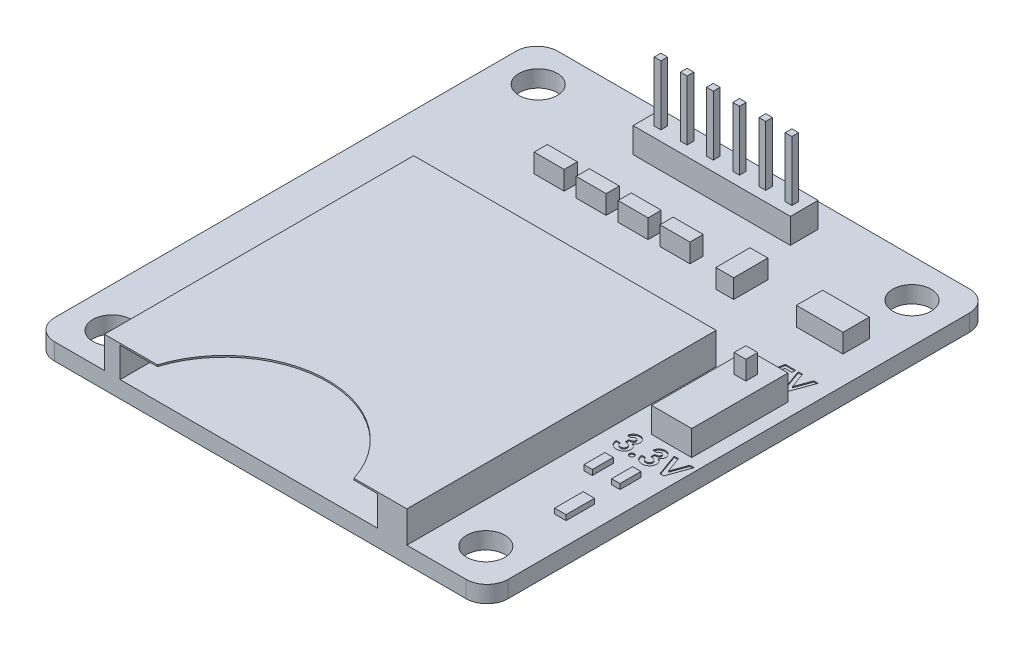
SolidWorks part; units mm, degrees
material "policarbonato"
ref_plane "Alzado" through (0, 0, 0) normal (0, 0, 1) x (1, 0, 0)
ref_plane "Planta" through (0, 0, 0) normal (0, 1, 0) x (1, 0, 0)
ref_plane "Vista lateral" through (0, 0, 0) normal (1, 0, 0) x (0, 0, -1)
sketch "Sketch1" plane through (0, 0, 0) normal (0, 1, 0) x (1, 0, 0)
  line L0 (3.8, 44.325) -> (39.45, 44.325) construction
  line L1 (0, 0) -> (43.25, 0)
  line L2 (0, 0) -> (0, 48)
  line L3 (0, 48) -> (43.25, 48)
  line L4 (43.25, 0) -> (43.25, 48)
  line L5 (39.45, 44.325) -> (39.45, 3.675) construction
  line L6 (39.45, 3.675) -> (3.8, 3.675) construction
  line L7 (3.8, 3.675) -> (3.8, 44.325) construction
  line L8 (21.625, 44.325) -> (21.625, 48) construction
  line L9 (39.45, 24) -> (43.25, 24) construction
  circle A0 centre (3.8, 44.325) radius 1.825
  circle A1 centre (3.8, 3.675) radius 1.825
  circle A2 centre (39.45, 44.325) radius 1.825
  circle A3 centre (39.45, 3.675) radius 1.825
  dimension "D3" = 3.65
  dimension "D4" = 32
  dimension "D5" = 37
  dimension "D6" = 40.65
  dimension "D7" = 35.65
  dimension "D1" = 43.25
  dimension "D2" = 48
extrude "Boss-Extrude1" add sketch "Sketch1" along normal blind 1.6
sketch "Sketch2" plane through (0, 1.6, 0) normal (0, 1, 0) x (1, 0, 0)
  line L0 (0, 0) -> (43.25, 0) construction
  line L1 (6.75, 0) -> (11.8, 0)
  line L2 (6.75, 0) -> (6.75, 29.5)
  line L3 (6.75, 29.5) -> (35.6, 29.5)
  line L4 (35.6, 0) -> (35.6, 29.5)
  line L6 (21.175, 29.5) -> (21.175, 0) construction
  line L7 (30.55, 0) -> (35.6, 0)
  line L9 (0, 48) -> (0, 0) construction
  arc A0 (11.8, 0) -> (30.55, 0) centre (21.175, -2.976) cw
  point P9 (21.175, 6.86)
  dimension "D1" = 6.75
  dimension "D2" = 29.5
  dimension "D3" = 6.86
  dimension "D4" = 18.75
  dimension "D5" = 28.85
extrude "Boss-Extrude2" add sketch "Sketch2" along normal offset from surface (3 mm away) 4.6 up to face at (39.45, 0, -42.5)
sketch "Sketch3" plane through (0, 0, 0) normal (0, 0, 1) x (1, 0, 0)
  line L0 (30.55, 1.6) -> (11.8, 1.6) construction
  line L1 (8.25, 1.6) -> (32.8, 1.6)
  line L2 (8.25, 1.6) -> (8.25, 4.45)
  line L3 (8.25, 4.45) -> (32.8, 4.45)
  line L4 (32.8, 1.6) -> (32.8, 4.45)
  line L5 (6.75, 4.6) -> (11.8, 4.6) construction
  line L6 (35.6, 4.6) -> (35.6, 1.6) construction
  line L7 (6.75, 4.6) -> (6.75, 1.6) construction
  point P8 (35.6, 3.1)
  dimension "D1" = 0.15
  dimension "D2" = 2.8
  dimension "D3" = 1.5
extrude "Cut-Extrude1" cut sketch "Sketch3" against normal blind 21.6
sketch "Sketch4" plane through (0, 1.6, 0) normal (0, 1, 0) x (1, 0, 0)
  line L0 (0, 38) -> (43.25, 38) construction
  line L1 (11, 38) -> (13.86, 38)
  line L2 (11, 38) -> (11, 36.74)
  line L3 (11, 36.74) -> (13.86, 36.74)
  line L4 (13.86, 38) -> (13.86, 36.74)
  line L5 (15, 38) -> (17.86, 38)
  line L6 (15, 38) -> (15, 36.74)
  line L7 (15, 36.74) -> (17.86, 36.74)
  line L8 (17.86, 38) -> (17.86, 36.74)
  line L9 (19, 38) -> (21.86, 38)
  line L10 (19, 38) -> (19, 36.74)
  line L11 (19, 36.74) -> (21.86, 36.74)
  line L12 (21.86, 38) -> (21.86, 36.74)
  line L13 (23, 38) -> (25.86, 38)
  line L14 (23, 38) -> (23, 36.74)
  line L15 (23, 36.74) -> (25.86, 36.74)
  line L16 (25.86, 38) -> (25.86, 36.74)
  line L17 (30.8926, 39.1335) -> (29.1926, 39.1335)
  line L18 (30.8926, 39.1335) -> (30.8926, 35.8735)
  line L19 (30.8926, 35.8735) -> (29.1926, 35.8735)
  line L20 (29.1926, 39.1335) -> (29.1926, 35.8735)
  line L21 (36.162, 39.0917) -> (40.612, 39.0917)
  line L22 (36.162, 39.0917) -> (36.162, 36.5917)
  line L23 (36.162, 36.5917) -> (40.612, 36.5917)
  line L24 (40.612, 39.0917) -> (40.612, 36.5917)
  line L25 (37.8886, 16.5953) -> (38.6886, 16.5953)
  line L26 (37.8886, 16.5953) -> (37.8886, 14.5953)
  line L27 (37.8886, 14.5953) -> (38.6886, 14.5953)
  line L28 (38.6886, 16.5953) -> (38.6886, 14.5953)
  line L29 (40.3717, 16.7505) -> (41.1717, 16.7505)
  line L30 (40.3717, 16.7505) -> (40.3717, 14.7505)
  line L31 (40.3717, 14.7505) -> (41.1717, 14.7505)
  line L32 (41.1717, 16.7505) -> (41.1717, 14.7505)
  line L33 (40.0854, 9.6117) -> (41.169, 9.6117)
  line L34 (40.0854, 9.6117) -> (40.0854, 12.3275)
  line L35 (40.0854, 12.3275) -> (41.169, 12.3275)
  line L36 (41.169, 9.6117) -> (41.169, 12.3275)
  line L37 (0, 48) -> (0, 0) construction
  line L38 (43.25, 0) -> (43.25, 48) construction
  line L39 (43.25, 48) -> (0, 48) construction
  dimension "D1" = 10
  dimension "D2" = 1.26
  dimension "D3" = 2.86
  dimension "D4" = 1.14
  dimension "D5" = 1.14
  dimension "D6" = 1.14
  dimension "D7" = 11
  dimension "D8" = 1.26
  dimension "D9" = 1.26
  dimension "D10" = 1.26
  dimension "D11" = 1.7
  dimension "D12" = 3.26
  dimension "D13" = 4.45
  dimension "D14" = 2.5
  dimension "D15" = 2
  dimension "D16" = 0.8
extrude "Boss-Extrude3" add sketch "Sketch4" along normal blind 1.8 contours L4 L1 L2 L3 | L8 L5 L6 L7 | L12 L9 L10 L11 | L16 L13 L14 L15 | L18 L19 L20 L17 | L24 L23 L22 L21 region at (12.43, 1.6, -37.37) region at (16.43, 1.6, -37.37) region at (20.43, 1.6, -37.37) region at (24.43, 1.6, -37.37)
extrude "Saliente-Extruir1" add sketch "Sketch4<3>" along normal blind 0.5 separate body contours L33 L36 L35 L34 | L32 L29 L30 L31 | L28 L25 L26 L27 region at (38.2886, 1.6, -15.5953) region at (40.7717, 1.6, -15.7505) region at (40.6272, 1.6, -10.9696)
sketch "Sketch4<3>" plane through (0, 1.6, 0) normal (0, 1, 0) x (1, 0, 0) same geometry as "Sketch4"
sketch "Sketch5" plane through (0, 1.6, 0) normal (0, 1, 0) x (1, 0, 0)
  line L0 (43.25, 0) -> (43.25, 48) construction
  line L1 (14.125, 45.7) -> (29.125, 45.7)
  line L2 (14.125, 45.7) -> (14.125, 43.05)
  line L3 (14.125, 43.05) -> (29.125, 43.05)
  line L4 (29.125, 45.7) -> (29.125, 43.05)
  line L5 (38.11, 30) -> (41.95, 30)
  line L6 (38.11, 30) -> (38.11, 20.82)
  line L7 (38.11, 20.82) -> (41.95, 20.82)
  line L8 (41.95, 30) -> (41.95, 20.82)
  line L9 (43.25, 48) -> (0, 48) construction
  line L10 (35.6, 29.5) -> (6.75, 29.5) construction
  line L12 (21.625, 45.7) -> (21.625, 48) construction
  dimension "D1" = 15
  dimension "D2" = 2.65
  dimension "D3" = 9.18
  dimension "D4" = 3.84
  dimension "D6" = 2.3
  dimension "D7" = 1.3
  dimension "D8" = 0.5
extrude "Boss-Extrude4" add sketch "Sketch5" along normal blind 2.4
sketch "Sketch6" plane through (0, 4, 0) normal (0, 1, 0) x (1, 0, 0)
  line L0 (14.125, 45.7) -> (14.125, 43.05) construction
  line L1 (15.165, 44.66) -> (15.805, 44.66)
  line L2 (15.165, 44.66) -> (15.165, 44.02)
  line L3 (15.165, 44.02) -> (15.805, 44.02)
  line L4 (15.805, 44.66) -> (15.805, 44.02)
  line L5 (29.125, 45.7) -> (14.125, 45.7) construction
  line L6 (17.665, 44.02) -> (18.305, 44.02)
  line L7 (17.665, 44.66) -> (17.665, 44.02)
  line L8 (17.665, 44.66) -> (18.305, 44.66)
  line L9 (18.305, 44.66) -> (18.305, 44.02)
  line L10 (20.165, 44.02) -> (20.805, 44.02)
  line L11 (20.165, 44.66) -> (20.165, 44.02)
  line L12 (20.165, 44.66) -> (20.805, 44.66)
  line L13 (20.805, 44.66) -> (20.805, 44.02)
  line L14 (22.665, 44.02) -> (23.305, 44.02)
  line L15 (22.665, 44.66) -> (22.665, 44.02)
  line L16 (22.665, 44.66) -> (23.305, 44.66)
  line L17 (23.305, 44.66) -> (23.305, 44.02)
  line L18 (25.165, 44.02) -> (25.805, 44.02)
  line L19 (25.165, 44.66) -> (25.165, 44.02)
  line L20 (25.165, 44.66) -> (25.805, 44.66)
  line L21 (25.805, 44.66) -> (25.805, 44.02)
  line L22 (27.665, 44.02) -> (28.305, 44.02)
  line L23 (27.665, 44.66) -> (27.665, 44.02)
  line L24 (27.665, 44.66) -> (28.305, 44.66)
  line L25 (28.305, 44.66) -> (28.305, 44.02)
  dimension "D1" = 0.64
  dimension "D2" = 0.64
  dimension "D3" = 1.04
  dimension "D4" = 1.04
  dimension "D5" = 6
extrude "Boss-Extrude5" add sketch "Sketch6" along normal blind 5.7
sketch "Sketch7" plane through (0, 4, 0) normal (0, 1, 0) x (1, 0, 0)
  line L0 (38.11, 20.82) -> (41.95, 20.82) construction
  line L1 (39.4881, 27.32) -> (40.6129, 27.32)
  line L2 (39.4881, 27.32) -> (39.4881, 28.4448)
  line L3 (39.4881, 28.4448) -> (40.6129, 28.4448)
  line L4 (40.6129, 27.32) -> (40.6129, 28.4448)
  dimension "D1" = 1.1248
  dimension "D2" = 6.5
extrude "Boss-Extrude6" add sketch "Sketch7" along normal blind 1.8
fillet "Fillet1" radius 2 4 edges at (0, 0.8, 0) (43.25, 0.8, 0) (43.25, 0.8, -48) (0, 0.8, -48)
sketch "Sketch8" plane through (0, 0, 0) normal (0, 0, 1) x (1, 0, 0)
  line L0 (20.525, 1.95) -> (20.525, 1.6) construction
  line L1 (8.525, 1.95) -> (32.525, 1.95)
  line L2 (8.525, 1.95) -> (8.525, 3.95)
  line L3 (8.525, 3.95) -> (32.525, 3.95)
  line L4 (32.525, 1.95) -> (32.525, 3.95)
  line L5 (8.25, 1.6) -> (32.8, 1.6) construction
  line L6 (2, 0) -> (41.25, 0) construction
  dimension "D1" = 24
  dimension "D2" = 2
  dimension "D3" = 1.95
extrude "Boss-Extrude7" [suppressed] add sketch "Sketch8" along normal blind 5.6 and the other way blind 26.3
sketch "Croquis1" plane through (0, 1.6, 0) normal (0, 1, 0) x (1, 0, 0)
  text T0 "<b>5V</b>" font "Century Gothic" height in points 8
extrude "Cortar-Extruir1" cut sketch "Croquis1" against normal blind 0.1
sketch "Croquis2" plane through (0, 1.6, 0) normal (0, 1, 0) x (1, 0, 0)
  text T0 "<b>3.3V</b>" font "Century Gothic" height in points 8
extrude "Cortar-Extruir2" cut sketch "Croquis2" against normal blind 0.1
